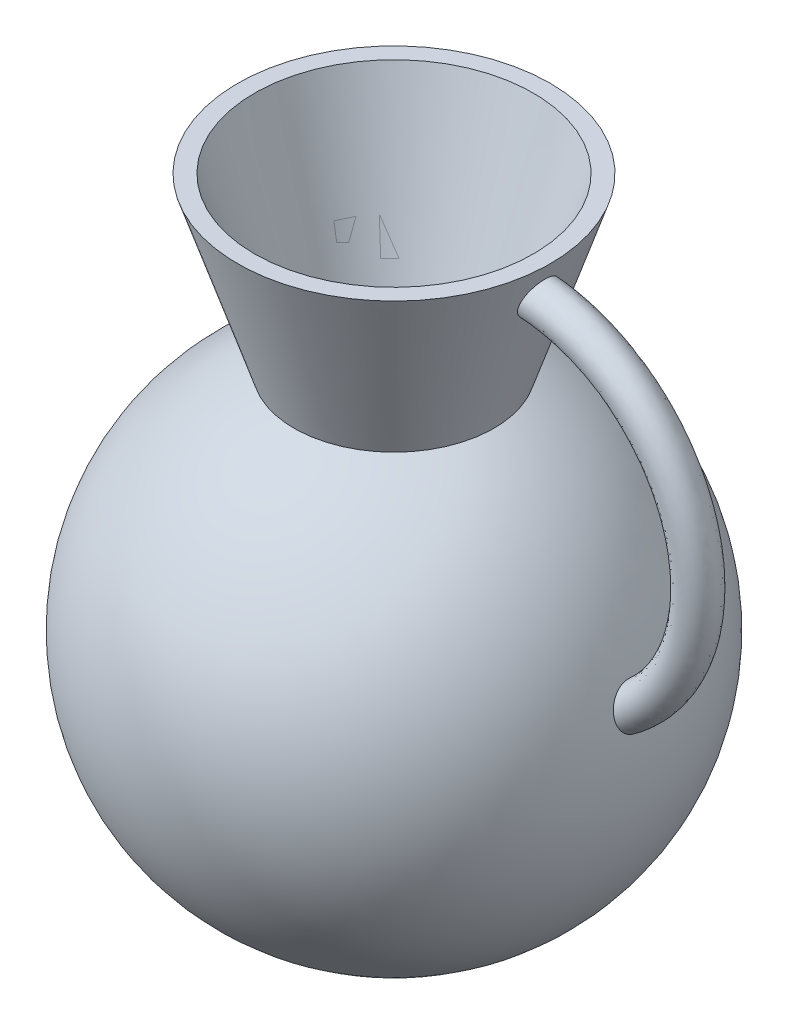
SolidWorks part; units mm, degrees
ref_plane "Front Plane" through (0, 0, 0) normal (0, 0, 1) x (1, 0, 0)
ref_plane "Top Plane" through (0, 0, 0) normal (0, 1, 0) x (1, 0, 0)
ref_plane "Right Plane" through (0, 0, 0) normal (1, 0, 0) x (0, 0, -1)
sketch "Sketch2" plane through (0, 0, 0) normal (0, 0, 1) x (1, 0, 0)
  line L0 (0, 0) -> (0, 99.8387) construction
  line L1 (0, 99.8387) -> (24.3265, 99.8387)
  line L2 (24.3265, 99.8387) -> (15.5607, 73.2754)
  line L3 (0, 0) -> (0, 99.8387)
  arc A0 (15.5607, 73.2754) -> (0, 0) centre (0, 38.2899) cw
  point P6 (0, 0)
  dimension "D2" = 38.2899
  dimension "D1" = 24.3265
  dimension "D3" = 99.8387
  dimension "D4" = 26.5633
revolve "Revolve1" add sketch "Sketch2" angle 360 about L0
shell "Shell1" thickness 2.5 removed face at (0, 99.8387, -24.3265)
sketch "Sketch3" plane through (0, 0, 0) normal (0, 0, 1) x (1, 0, 0)
  arc A0 (12.9895, 93.4945) -> (32.7757, 43.8022) centre (20.399, 67.6595) cw
ref_plane "Plane1" through (43.3447, 17.2588, 0) normal (0.9291, 0.3699, 0) x (0, 0, -1)
surface "Surface-Offset1" parameters "D1"=0
sketch "Sketch4" plane through (43.3447, 17.2588, 0) normal (0.9291, 0.3699, 0) x (0, 0, -1)
  circle A0 centre (0, 82.0568) radius 3
  dimension "D1" = 6
sweep "Sweep1" add profiles "Sketch4" path "Sketch3"
other "SurfaceCut3" flip cut yes
